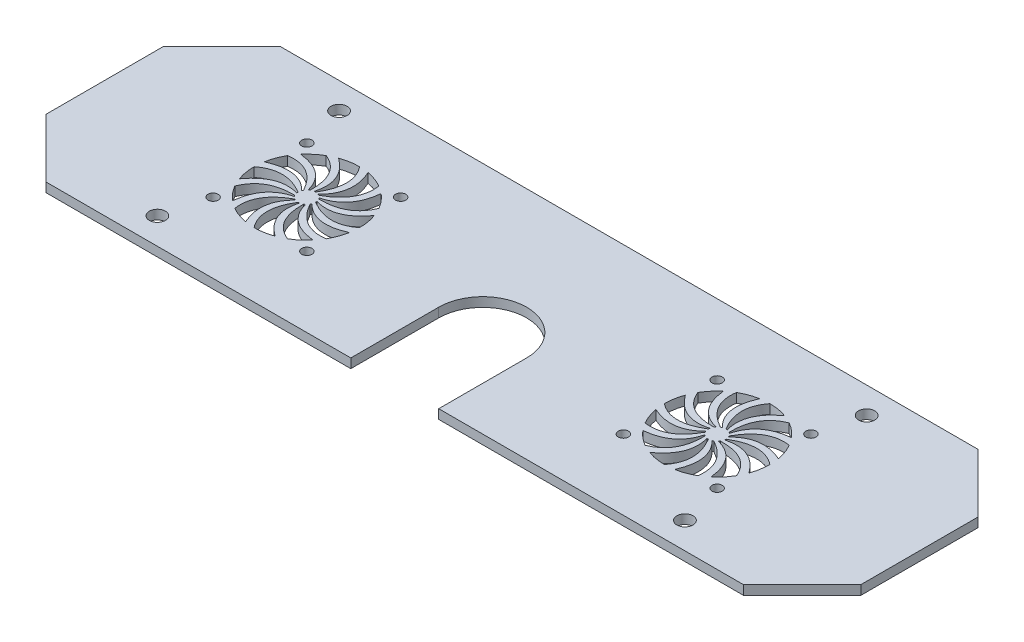
SolidWorks part; units mm, degrees
ref_plane "Front Plane" through (0, 0, 0) normal (0, 0, 1) x (1, 0, 0)
ref_plane "Top Plane" through (0, 0, 0) normal (0, 1, 0) x (1, 0, 0)
ref_plane "Right Plane" through (0, 0, 0) normal (1, 0, 0) x (0, 0, -1)
sketch "Sketch1" plane through (0, 0, 0) normal (0, 1, 0) x (1, 0, 0)
  line L1 (139, -40) -> (-139, -40)
  line L2 (139, -40) -> (139, 40)
  line L3 (139, 40) -> (-139, 40)
  line L4 (-139, -40) -> (-139, 40)
  line L5 (139, -40) -> (-139, 40) construction
  line L6 (139, 40) -> (-139, -40) construction
  point P0 (0, 0)
  dimension "D1" = 278
  dimension "D2" = 80
extrude "Boss-Extrude1" add sketch "Sketch1" along normal blind 3.175
chamfer "Chamfer1" distance 20 angle 45 4 edges at (139, 1.5875, 40) (139, 1.5875, -40) (-139, 1.5875, -40) (-139, 1.5875, 40)
sketch "Sketch2" plane through (0, 3.175, 0) normal (0, 1, 0) x (1, 0, 0)
  line L0 (-89.7765, 0) -> (-62.0345, 0) construction
  line L1 (-70, 0) -> (-70, 32.1983) construction
  line L2 (0, 91.4041) -> (0, -93.8215) construction
  circle A0 centre (-86, 16) radius 1.75
  circle A1 centre (-54, 16) radius 1.75
  circle A2 centre (-86, -16) radius 1.75
  circle A3 centre (-54, -16) radius 1.75
  circle A4 centre (54, -16) radius 1.75
  circle A5 centre (86, -16) radius 1.75
  circle A6 centre (54, 16) radius 1.75
  circle A7 centre (86, 16) radius 1.75
  dimension "D4" = 3.5
  dimension "D1" = 70
  dimension "D2" = 32
  dimension "D3" = 32
extrude "Cut-Extrude1" cut sketch "Sketch2" against normal blind 10
sketch "Sketch3" plane through (0, 3.175, 0) normal (0, 1, 0) x (1, 0, 0)
  line L0 (-166.5325, 0) -> (239.9445, 0) construction
  line L1 (0, 62.0423) -> (0, -51.4035) construction
  line L2 (119, 40) -> (-119, 40) construction
  circle A0 centre (-90, 31) radius 2.75
  circle A1 centre (-90, -31) radius 2.75
  circle A2 centre (90, -31) radius 2.75
  circle A3 centre (90, 31) radius 2.75
  dimension "D1" = 5.5
  dimension "D2" = 90
  dimension "D3" = 9
extrude "Cut-Extrude2" cut sketch "Sketch3" against normal blind 10
sketch "Sketch4" plane through (0, 3.175, 0) normal (0, 1, 0) x (1, 0, 0)
  line L1 (0, 0) -> (0, -40) construction
  line L3 (15, -40) -> (-15, -40)
  line L4 (-119, -40) -> (119, -40) construction
  line L5 (-15, -40) -> (-15, -10)
  line L6 (15, -40) -> (15, -10)
  arc A0 (15, -10) -> (-15, -10) centre (0, -10) ccw
  point P11 (0, -40)
  dimension "D1" = 15
  dimension "D2" = 30
extrude "Cut-Extrude3" cut sketch "Sketch4" against normal blind 10
sketch "Sketch6" plane through (0, 3.175, 0) normal (0, 1, 0) x (1, 0, 0)
  line L0 (-54, 16) -> (-86, -16) construction
  line L1 (-86, 16) -> (-54, -16) construction
  line L4 (-200166.5325, 0) -> (200239.9445, 0) construction
  line L5 (0, 47.7309) -> (0, -11.7205) construction
  arc A0 (-67, 0) -> (-67.0404, 0.4904) centre (-70, 0) ccw
  arc A1 (-52, 0) -> (-53.061, 6.0885) centre (-70, 0) ccw
  spline S0 degree 2 poles (-67, 0) (-58.536, -5.1383) (-52, 0) knots 0 0 0 1 1 1
  spline S1 degree 2 poles (-67.0404, 0.4904) (-58.8313, -1.8438) (-53.061, 6.0885) knots 0 0 0 1 1 1
  point P10 (-70, 0)
  dimension "D1" = 18
  dimension "D2" = 3
  dimension "D3" = 16.1946
  dimension "D4" = 16.1098
ref_axis "Axis1" through (-70, 3.175, 0) along (0, 1, 0)
extrude "Cut-Extrude8" cut sketch "Sketch6" against normal blind 10
pattern_circular "CirPattern1" count 12 over 360 about axis through (-70, 3.175, 0) along (0, 1, 0) of "Cut-Extrude8"
mirror "Mirror1" about plane through (0, 0, 0) normal (1, 0, 0) of "CirPattern1", "Cut-Extrude8"
equation "\"connector_D1\" = 70 'the big holes diameter"
equation "\"mtg_hole_D\" = 5.5 'mounting holes"
equation "\"mtg_dfc\" = 40 'mounting hole distance from center"
equation "\"plate_thickness\" = 6.35 'thickness of the plate "
equation "\"t_height\" = 200"
equation "\"t_width\" = 240"
equation "\"t_length\" = 240"
equation "\"plate_hole_from_edge\" = 9"
equation "\"plate_spacing\" = 1"
equation "\"front_plate_height\" = \"t_height\" + 38"
equation "\"front_plate_width\" = \"t_width\" + 38"
equation "\"side_plate_height\" = \"front_plate_height\""
equation "\"side_plate_length\" = \"t_length\" + 38"
equation "\"top_plate_width\" = \"front_plate_width\""
equation "\"top_plate_length\" = \"side_plate_length\""
equation "\"itx_support_t_slot_length\" = \"t_width\" + (2 * 20.5)"
equation "\"locomotion_length\" = \"t_length\""
equation "\"locomotion_width\" = \"t_width\""
equation "\"locomotion_height\" = 40"
equation "\"itx_mtg_hole_spacing\" = 40"
equation "\"emg30_bracket_hole_len\" = 60"
equation "\"emg30_bracket_hole_wid\" = 11"
equation "\"perce_t_height\" = 50"
equation "\"perce_top_width\" = 170"
equation "\"perce_mtg_hole_spacing\" = \"perce_top_width\" - 20"
equation "\"D1@Sketch1\"=\"side_plate_length\""
equation "\"D1@Boss-Extrude1\"=.125in"
equation "\"D1@Sketch3\"=\"mtg_hole_D\""
equation "\"D3@Sketch3\"=\"plate_hole_from_edge\""
